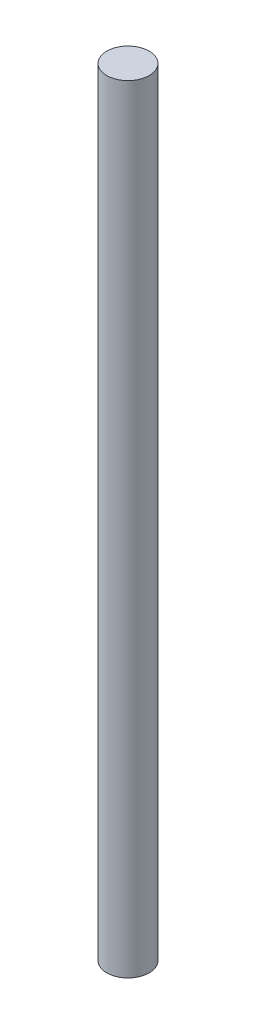
SolidWorks part; units mm, degrees
ref_plane "Front Plane" through (0, 0, 0) normal (0, 0, 1) x (1, 0, 0)
ref_plane "Top Plane" through (0, 0, 0) normal (0, 1, 0) x (1, 0, 0)
ref_plane "Right Plane" through (0, 0, 0) normal (1, 0, 0) x (0, 0, -1)
sketch "Sketch1" plane through (0, 0, 0) normal (0, 1, 0) x (1, 0, 0)
  circle A0 centre (0, 0) radius 1.4732
  dimension "D1" = 2.9464
extrude "Boss-Extrude1" add sketch "Sketch1" along normal blind 53.975
